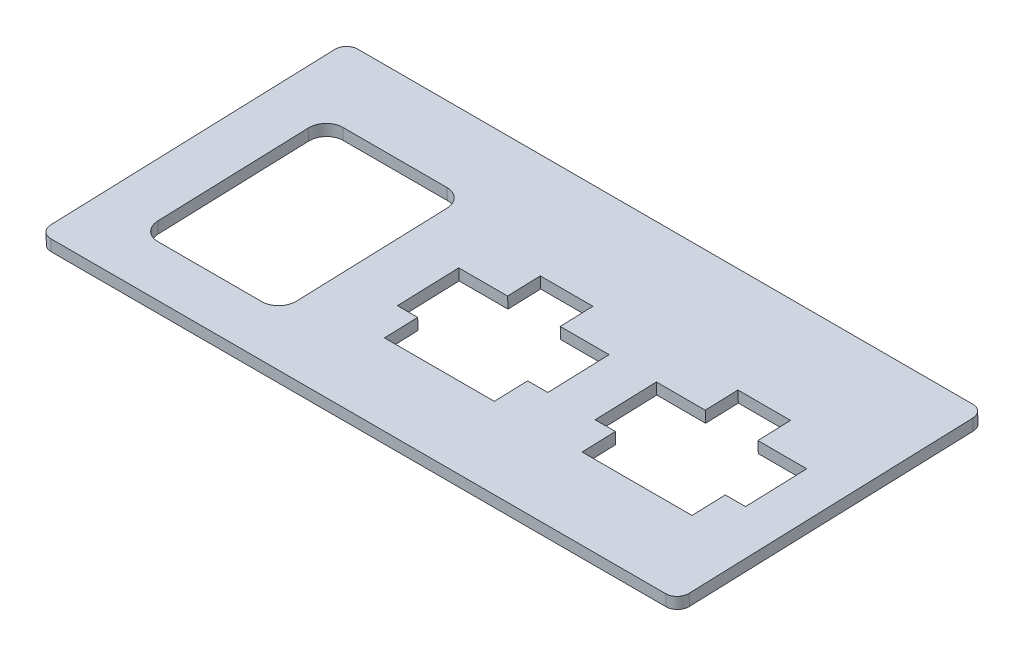
SolidWorks part; units mm, degrees
ref_plane "Front Plane" through (0, 0, 0) normal (0, 0, 1) x (1, 0, 0)
ref_plane "Top Plane" through (0, 0, 0) normal (0, 1, 0) x (1, 0, 0)
ref_plane "Right Plane" through (0, 0, 0) normal (1, 0, 0) x (0, 0, -1)
sketch "Sketch1" plane through (0, -68.9908, -2.4092) normal (0, 0.9994, 0.0349) x (1, 0, 0)
  line L1 (-53.6759, -2.8069) -> (-56.175, -2.8069) construction
  line L2 (55.275, 48.7944) -> (-55.275, 48.7944) construction
  line L8 (-55.175, -4.3069) -> (55.175, -4.3069)
  line L9 (55.175, -4.3069) -> (55.175, 48.7944)
  line L10 (55.175, 48.7944) -> (-55.175, 48.7944)
  line L11 (-55.175, 48.7944) -> (-55.175, -4.3069)
  dimension "D1" = 1.5
  dimension "D2" = 3.0034
  dimension "D3" = 3.0034
extrude "Boss-Extrude1" add sketch "Sketch1" along normal blind 2
sketch "Sketch2" plane through (0, -68.9908, -2.4092) normal (0, -0.9994, -0.0349) x (1, 0, 0)
  line L0 (-4.05, -25.5688) -> (-4.05, -31.2188)
  line L1 (-43.175, -4.2188) -> (-25.175, -4.2188)
  line L2 (-46.175, -7.2188) -> (-46.175, -33.2188)
  line L3 (-43.175, -36.2188) -> (-25.175, -36.2188)
  line L4 (-22.175, -7.2188) -> (-22.175, -33.2188)
  line L5 (-12.5, -14.9688) -> (-9, -14.9688)
  line L6 (-12.5, -14.9688) -> (-12.5, -25.5688)
  line L7 (-12.5, -25.5688) -> (-4.05, -25.5688)
  line L8 (13.5, -14.9688) -> (13.5, -25.5688)
  line L9 (-9, -9.2188) -> (10, -9.2188)
  line L10 (-9, -9.2188) -> (-9, -14.9688)
  line L11 (-4.05, -31.2188) -> (5.05, -31.2188)
  line L12 (10, -9.2188) -> (10, -14.9688)
  line L13 (10, -14.9688) -> (13.5, -14.9688)
  line L14 (5.05, -25.5688) -> (5.05, -31.2188)
  line L15 (5.05, -25.5688) -> (13.5, -25.5688)
  line L16 (-13, -6.7188) -> (14, -33.7188) construction
  line L17 (-13, -6.7188) -> (14, -6.7188) construction
  line L18 (-13, -6.7188) -> (-13, -33.7188) construction
  line L19 (-13, -33.7188) -> (14, -33.7188) construction
  line L20 (14, -6.7188) -> (14, -33.7188) construction
  line L21 (17.5875, 3.7502) -> (17.5875, -36.664) construction
  line L22 (47.675, -20.2688) -> (21.675, -20.2688) construction
  line L23 (34.675, -9.2188) -> (34.675, -31.2188) construction
  line L24 (21.175, -6.7188) -> (21.175, -33.7188) construction
  line L25 (48.175, -33.7188) -> (21.175, -33.7188) construction
  line L26 (48.175, -6.7188) -> (48.175, -33.7188) construction
  line L27 (48.175, -6.7188) -> (21.175, -6.7188) construction
  line L28 (-48.175, -20.2188) -> (-46.175, -20.2188) construction
  line L29 (-48.175, -2.2188) -> (-20.175, -2.2188) construction
  line L30 (-48.175, -2.2188) -> (-48.175, -38.2188) construction
  line L31 (-48.175, -38.2188) -> (-20.175, -38.2188) construction
  line L32 (-20.175, -2.2188) -> (-20.175, -38.2188) construction
  line L33 (-34.175, -4.2188) -> (-34.175, -2.2188) construction
  line L34 (0.5, -9.2188) -> (0.5, -31.2188) construction
  line L35 (-12.5, -20.2688) -> (13.5, -20.2688) construction
  line L36 (48.175, -6.7188) -> (21.175, -33.7188) construction
  line L37 (30.125, -25.5688) -> (21.675, -25.5688)
  line L38 (30.125, -25.5688) -> (30.125, -31.2188)
  line L39 (25.175, -14.9688) -> (21.675, -14.9688)
  line L40 (25.175, -9.2188) -> (25.175, -14.9688)
  line L41 (39.225, -31.2188) -> (30.125, -31.2188)
  line L42 (44.175, -9.2188) -> (44.175, -14.9688)
  line L43 (44.175, -9.2188) -> (25.175, -9.2188)
  line L44 (21.675, -14.9688) -> (21.675, -25.5688)
  line L45 (47.675, -25.5688) -> (39.225, -25.5688)
  line L46 (47.675, -14.9688) -> (47.675, -25.5688)
  line L47 (47.675, -14.9688) -> (44.175, -14.9688)
  line L48 (39.225, -25.5688) -> (39.225, -31.2188)
  line L49 (21.175, -20.2188) -> (14, -20.2188) construction
  line L50 (-55.175, 4.3069) -> (55.175, 4.3069) construction
  line L51 (48.175, -20.2188) -> (52.175, -20.2188) construction
  line L52 (55.175, 4.3069) -> (55.175, -48.7944) construction
  line L53 (-46.6517, -44.7445) -> (46.6517, -44.7445) construction
  line L54 (-13, -20.2188) -> (-20.175, -20.2188) construction
  line L55 (-34.175, -2.2188) -> (-34.175, 4.3069) construction
  line L56 (-34.175, -38.2188) -> (-34.175, -44.7445) construction
  line L57 (-55.175, -48.7944) -> (-55.175, 4.3069) construction
  line L58 (-48.175, -20.2188) -> (-52.175, -20.2188) construction
  arc A0 (-46.175, -33.2188) -> (-43.175, -36.2188) centre (-43.175, -33.2188) ccw
  arc A1 (-25.175, -36.2188) -> (-22.175, -33.2188) centre (-25.175, -33.2188) ccw
  arc A2 (-25.175, -4.2188) -> (-22.175, -7.2188) centre (-25.175, -7.2188) cw
  arc A3 (-43.175, -4.2188) -> (-46.175, -7.2188) centre (-43.175, -7.2188) ccw
  point P28 (0.5, -20.2188)
  point P63 (34.675, -20.2188)
  dimension "D1" = 3
  dimension "D2" = 32
  dimension "D3" = 24
  dimension "D4" = 28
  dimension "D5" = 36
  dimension "D6" = 26
  dimension "D7" = 22
  dimension "D8" = 10.6
  dimension "D9" = 19
  dimension "D10" = 9.1
  dimension "D11" = 5.75
  dimension "D12" = 27
  dimension "D13" = 27
  dimension "D14" = 4
  dimension "D15" = 3
  dimension "D16" = 3
extrude "Cut-Extrude1" cut sketch "Sketch2" against normal up to next
fillet "Fillet1" radius 2 4 edges at (-55.175, -68.1418, 1.93) (55.175, -68.1418, 1.93) (55.175, -66.2886, -51.139) (-55.175, -66.2886, -51.139)
